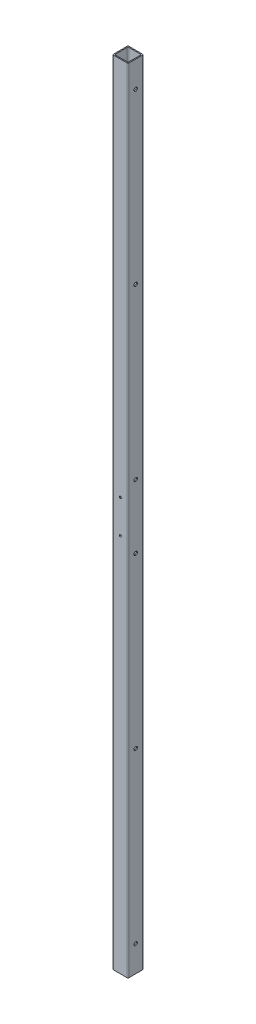
SolidWorks part; units mm, degrees
ref_plane "Front Plane" through (0, 0, 0) normal (0, 0, 1) x (1, 0, 0)
ref_plane "Top Plane" through (0, 0, 0) normal (0, 1, 0) x (1, 0, 0)
ref_plane "Right Plane" through (0, 0, 0) normal (1, 0, 0) x (0, 0, -1)
sketch "Sketch1" plane through (0, 0, 0) normal (0, 1, 0) x (1, 0, 0)
  line L0 (11.049, -11.049) -> (11.049, 11.049)
  line L1 (-12.7, -12.7) -> (12.7, -12.7)
  line L2 (-12.7, -12.7) -> (-12.7, 12.7)
  line L3 (-12.7, 12.7) -> (12.7, 12.7)
  line L4 (12.7, -12.7) -> (12.7, 12.7)
  line L5 (-12.7, -12.7) -> (12.7, 12.7) construction
  line L6 (-12.7, 12.7) -> (12.7, -12.7) construction
  line L7 (-11.049, 11.049) -> (11.049, 11.049)
  line L8 (-11.049, -11.049) -> (-11.049, 11.049)
  line L9 (-11.049, -11.049) -> (11.049, -11.049)
  point P0 (0, 0)
  dimension "D1" = 25.4
  dimension "D2" = 1.651
extrude "Boss-Extrude1" add sketch "Sketch1" along normal blind 1309.624
fillet "Fillet1" radius 1.27 8 edges at (-12.7, 654.812, 12.7) (-12.7, 654.812, -12.7) (12.7, 654.812, -12.7) (12.7, 654.812, 12.7) (-11.049, 654.812, -11.049) (11.049, 654.812, 11.049) (11.049, 654.812, -11.049) (-11.049, 654.812, 11.049)
hole_wizard "#1 (0.228) Diameter Hole1" positions "Sketch2" profile "Sketch3" hole size "#1" standard "ANSI Inch" end condition through all
sketch "Sketch2" plane through (12.7, 0, 0) normal (1, 0, 0) x (0, 0, -1)
  line L0 (0, 1309.624) -> (0, 0) construction
  line L1 (-11.43, 1309.624) -> (11.43, 1309.624) construction
  line L2 (11.43, 0) -> (-11.43, 0) construction
  line L4 (-11.43, 0) -> (11.43, 0) construction
  point P8 (0, 1266.444)
  point P82 (0, 987.044)
  point P83 (0, 707.644)
  point P84 (0, 43.18)
  point P107 (0, 322.58)
  point P108 (0, 601.98)
  dimension "D1" = 43.18
  dimension "D3" = 43.18
  dimension "D5" = 322.58
  dimension "D6" = 707.644
  dimension "D2" = 3
  dimension "D4" = 3
sketch "Sketch3" plane through (12.7, 601.98, 0) normal (0, 1, 0) x (0, 0, -1)
  line L0 (0, 0) -> (0, 25.4)
  line L1 (0, 25.4) -> (2.8956, 25.4)
  line L2 (2.8956, 25.4) -> (2.8956, 0)
  line L5 (2.8956, 0) -> (0, 0)
  line L11 (0, -6.35) -> (0, 107.95) construction
  dimension "Thru Hole Dia." = 5.7912
  dimension "Thru Hole Depth" = 25.4
hole_wizard "#8-32 Tapped Hole1" positions "Sketch4" profile "Sketch5" tap size "#8-32" standard "ANSI Inch" end condition through all
sketch "Sketch4" plane through (0, 0, -12.7) normal (0, 0, -1) x (-1, 0, 0)
  line L0 (-11.43, 0) -> (11.43, 1309.624) construction
  line L2 (0, 654.812) -> (-11.43, 654.812) construction
  line L3 (-11.43, 1309.624) -> (-11.43, 0) construction
  line L5 (0, 654.812) -> (0, 842.9154) construction
  line L6 (0, 654.812) -> (0, 575.682) construction
  point P19 (0, 682.244)
  point P25 (0, 627.38)
  dimension "D1" = 27.432
  dimension "D2" = 27.432
sketch "Sketch5" plane through (0, 627.38, -12.7) normal (1, 0, 0) x (0, 1, 0)
  line L0 (0, 0) -> (0, 25.4)
  line L1 (0, 25.4) -> (1.7272, 25.4)
  line L2 (1.7272, 25.4) -> (1.7272, 0)
  line L5 (1.7272, 0) -> (0, 0)
  line L11 (0, -6.35) -> (0, 107.95) construction
  dimension "Thru Tap Drill Dia." = 3.4544
  dimension "Thru Tap Drill Depth" = 25.4
cosmetic thread "Hole Thread1" parameters "D2"=4.1656
cosmetic thread "Hole Thread2" parameters "D2"=4.1656
